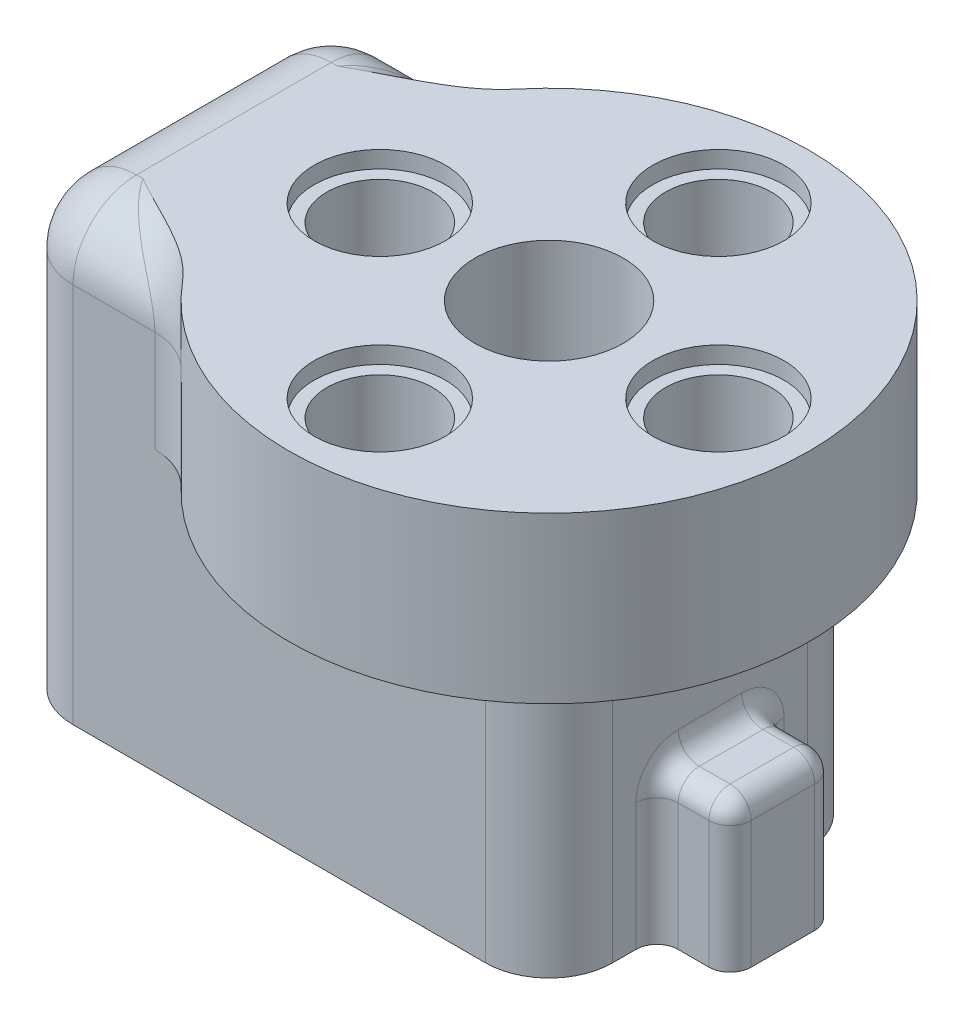
SolidWorks part; units mm, degrees
ref_plane "前视基准面" through (0, 0, 0) normal (0, 0, 1) x (1, 0, 0)
ref_plane "上视基准面" through (0, 0, 0) normal (0, 1, 0) x (1, 0, 0)
ref_plane "右视基准面" through (0, 0, 0) normal (1, 0, 0) x (0, 0, -1)
other "Configuration Table"
sketch "草图1" plane through (0, 0, 0) normal (0, 1, 0) x (1, 0, 0)
  line L0 (-15.3223, -3.0533) -> (10.1777, -3.0533) construction
  line L1 (-15.3223, 4.5467) -> (10.1777, 4.5467)
  line L2 (-15.3223, 4.5467) -> (-15.3223, -10.6533)
  line L3 (-15.3223, -10.6533) -> (10.1777, -10.6533)
  line L4 (10.1777, 4.5467) -> (10.1777, -10.6533)
  line L5 (-13.8223, -7.433) -> (-15.3223, -7.433)
  line L6 (-13.8223, 3.0467) -> (8.6777, 3.0467)
  line L7 (-13.8223, 3.0467) -> (-13.8223, -9.1533)
  line L8 (-13.8223, -9.1533) -> (8.6777, -9.1533)
  line L9 (8.6777, 3.0467) -> (8.6777, -9.1533)
  line L10 (8.6777, -7.433) -> (10.1777, -7.433)
  line L11 (2.5777, 9.2467) -> (17.4245, 9.2467) construction
  line L12 (2.5777, 8.0467) -> (16.7706, 8.0467) construction
  circle A0 centre (2.5777, -3.0533) radius 3.5
  circle A1 centre (-5.4223, -3.0533) radius 2.5
  circle A2 centre (-5.4223, -3.0533) radius 3.1
  circle A3 centre (2.5777, -3.0533) radius 6.1 construction
  circle A4 centre (2.5777, 4.9467) radius 2.5
  circle A5 centre (2.5777, 4.9467) radius 3.1
  circle A6 centre (10.5777, -3.0533) radius 2.5
  circle A7 centre (10.5777, -3.0533) radius 3.1
  circle A8 centre (2.5777, -11.0533) radius 2.5
  circle A9 centre (2.5777, -11.0533) radius 3.1
  circle A10 centre (2.5777, -3.0533) radius 12.3
  point P33 (2.5777, -3.0533)
  dimension "D1" = 7
  dimension "D2" = 5
  dimension "D3" = 6.2
  dimension "D5" = 15.2
  dimension "D10" = 1.2
  dimension "D4" = 8
  dimension "D6" = 25.5
  dimension "D7" = 22.5
  dimension "D8" = 12.2
  dimension "D9" = 4
extrude "凸台-拉伸1" add sketch "草图1" against normal blind 21 contours A0 | L0 A0 | L1 L4 L3 L2 region at (2.5777, 0, 3.0533)
extrude "凸台-拉伸4" add sketch "草图1<9>" against normal blind 7.8 contours A0 | A10 region at (2.5777, 0, 3.0533)
sketch "草图1<9>" plane through (0, 0, 0) normal (0, 1, 0) x (1, 0, 0) same geometry as "草图1"
extrude "切除-拉伸3" cut sketch "草图1<5>" against normal blind 7.8 contours A8 | A6 | A4 | A1
sketch "草图1<5>" plane through (0, 0, 0) normal (0, 1, 0) x (1, 0, 0) same geometry as "草图1"
extrude "切除-拉伸4" cut sketch "草图1<6>" against normal blind 0.8 contours A2 A1 | L3 A9 A8 | L8 A9 L3 A8 | L3 A9 L8 A8 | L8 A9 A8 | L4 A7 A6 | L9 A7 L4 A6 | L9 A7 A6 | L4 A7 L9 A6 | L1 A5 A4 | L1 A5 L6 A4 | L6 A5 A4 | L6 A5 L1 A4 region at (2.3819, 0, -7.9692) region at (0.0944, 0, -3.7597) region at (2.5777, 0, -2.4389) region at (5.0611, 0, -3.7597) region at (0.0944, 0, 9.8662) region at (-0.1932, 0, 10.7244) region at (2.5777, 0, 8.5454) region at (5.0611, 0, 9.8662) region at (12.5765, 0, 0.7776) region at (9.3907, 0, 0.5699) region at (8.0699, 0, 3.0533) region at (9.3907, 0, 5.5366) region at (-8.4346, 0, 3.0533)
sketch "草图1<6>" plane through (0, 0, 0) normal (0, 1, 0) x (1, 0, 0) same geometry as "草图1"
extrude "切除-拉伸1" cut sketch "草图1<4>" along normal blind 13.2 from surface contours L7 L8 L9 L6 starting at face at (2.5777, -21, 6.5533)
sketch "草图1<4>" plane through (0, 0, 0) normal (0, 1, 0) x (1, 0, 0) same geometry as "草图1"
extrude "切除-拉伸5" cut sketch "草图1<8>" along normal blind 0.8 from surface contours A2 A1 | L6 A5 A4 | L6 A5 L1 A4 | L1 A5 A4 | L1 A5 L6 A4 | L3 A9 A8 | L3 A9 L8 A8 | L8 A9 A8 | L8 A9 L3 A8 | L4 A7 A6 | L9 A7 L4 A6 | L9 A7 A6 | L4 A7 L9 A6 region at (2.3819, 0, -7.9692) region at (0.0944, 0, -3.7597) region at (2.5777, 0, -2.4389) region at (5.0611, 0, -3.7597) region at (0.0944, 0, 9.8662) region at (-0.1932, 0, 10.7244) region at (2.5777, 0, 8.5454) region at (5.0611, 0, 9.8662) region at (12.5765, 0, 0.7776) region at (9.3907, 0, 0.5699) region at (8.0699, 0, 3.0533) region at (9.3907, 0, 5.5366) region at (-8.4346, 0, 3.0533) starting at face at (-5.4223, -7.8, 5.5533)
sketch "草图1<8>" plane through (0, 0, 0) normal (0, 1, 0) x (1, 0, 0) same geometry as "草图1"
sketch "草图3" plane through (-15.3223, 0, 0) normal (-1, 0, 0) x (0, 0, 1)
  line L0 (-4.5467, -21) -> (10.6533, -21) construction
  line L1 (0.5533, -21) -> (5.5533, -21)
  line L2 (0.5533, -21) -> (0.5533, -14)
  line L3 (0.5533, -14) -> (5.5533, -14)
  line L4 (5.5533, -21) -> (5.5533, -14)
  line L5 (3.0533, 0) -> (3.0533, -14) construction
  line L6 (-4.5467, 0) -> (10.6533, 0) construction
  dimension "D1" = 7
  dimension "D2" = 5
extrude "凸台-拉伸2" add sketch "草图3" along normal blind 3.45
sketch "草图8" plane through (10.1777, 0, 0) normal (1, 0, 0) x (0, 0, -1)
  line L0 (4.5467, -21) -> (-10.6533, -21) construction
  line L1 (-0.5533, -21) -> (-5.5533, -21)
  line L2 (-0.5533, -21) -> (-0.5533, -14)
  line L3 (-0.5533, -14) -> (-5.5533, -14)
  line L4 (-5.5533, -21) -> (-5.5533, -14)
  line L5 (-3.0533, 0) -> (-3.0533, -14) construction
  line L6 (4.5467, 0) -> (-10.6533, 0) construction
  dimension "D1" = 5
  dimension "D2" = 7
extrude "凸台-拉伸3" add sketch "草图8" along normal blind 3.45
sketch "草图5" plane through (0, -14, 0) normal (0, 1, 0) x (1, 0, 0)
  line L0 (-18.7723, -3.0533) -> (13.6277, -3.0533) construction
  line L1 (-18.7723, -5.5533) -> (-18.7723, -0.5533) construction
  line L3 (-11.2078, 4.5467) -> (-11.2078, -10.6533) construction
  line L4 (-15.3223, 4.5467) -> (-7.0933, 4.5467) construction
  line L5 (-15.3223, -10.6533) -> (-7.0933, -10.6533) construction
  line L6 (13.6277, -5.5533) -> (13.6277, -0.5533) construction
  circle A0 centre (-16.6723, -3.0533) radius 0.85
  circle A1 centre (-5.7433, -3.0533) radius 0.85
  circle A2 centre (11.5277, -3.0533) radius 0.85
  dimension "D1" = 1.7
  dimension "D2" = 2.1
  dimension "D3" = 2.1
extrude "切除-拉伸2" cut sketch "草图5" along normal blind 6 from surface contours A0 | A2 starting at face at (-2.5723, -21, 3.0533)
fillet "圆角1" radius 1 16 edges at (-15.3223, -17.5, 5.5533) (-15.3223, -17.5, 0.5533) (10.1777, -17.5, 0.5533) (10.1777, -17.5, 5.5533) (-17.0473, -14, 5.5533) (-17.0473, -14, 0.5533) (-18.7723, -14, 3.0533) (-18.7723, -17.5, 5.5533) (-18.7723, -17.5, 0.5533) (11.9027, -14, 0.5533) (11.9027, -14, 5.5533) (13.6277, -17.5, 5.5533) (13.6277, -14, 3.0533) (13.6277, -17.5, 0.5533) (10.1777, -14, 3.0533) (-15.3223, -14, 3.0533)
fillet "圆角3" radius 3 7 edges at (10.1777, -14.4, 10.6533) (10.1777, -14.4, -4.5467) (-15.3223, -10.5, -4.5467) (-15.3223, -10.5, 10.6533) (-11.2078, 0, -4.5467) (-11.2078, 0, 10.6533) (-15.3223, 0, 3.0533)
fillet "圆角4" radius 3 4 edges at (-7.4438, -1.3902, -4.0783) (-7.8074, -0.7557, 9.6441) (-7.0933, -5.4, -4.5467) (-7.0933, -5.4, 10.6533)
